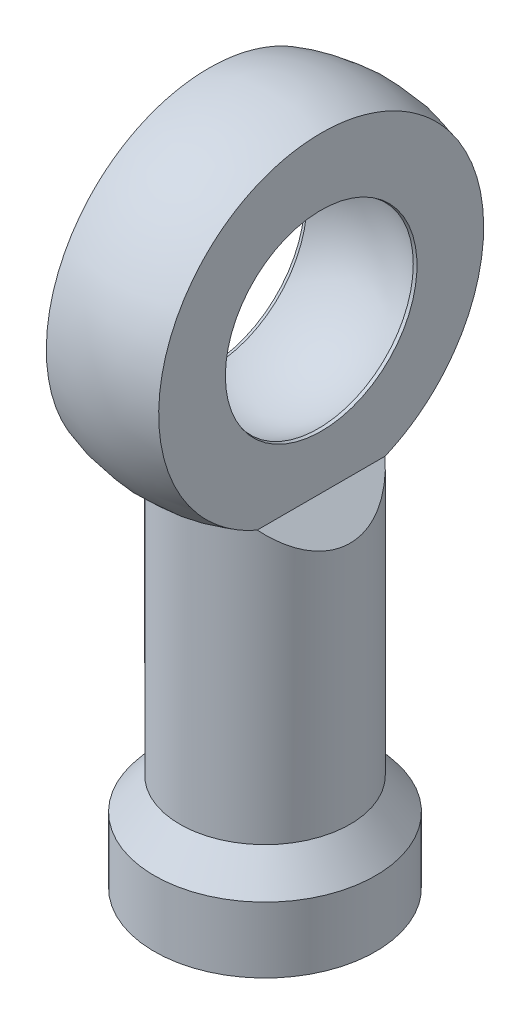
SolidWorks part; units mm, degrees
material "Rotulas (CuZn40)"
ref_plane "Alzado" through (0, 0, 0) normal (0, 0, 1) x (1, 0, 0)
ref_plane "Planta" through (0, 0, 0) normal (0, 1, 0) x (1, 0, 0)
ref_plane "Vista lateral" through (0, 0, 0) normal (1, 0, 0) x (0, 0, -1)
sketch "Croquis1" plane through (0, 0, 0) normal (0, 0, 1) x (1, 0, 0)
  line L1 (-5, -8.7755) -> (-5, -24.7755)
  line L2 (-5, -24.7755) -> (-6.5, -26.6381)
  line L3 (-6.5, -26.6381) -> (-6.5, -30.5)
  line L4 (-6.5, -30.5) -> (0, -30.5)
  line L5 (0, 10.1) -> (0, 6.4)
  line L6 (0, -6.4) -> (0, -30.5)
  arc A0 (0, 6.4) -> (0, -6.4) centre (0, 0) ccw
  arc A1 (0, 10.1) -> (-5, -8.7755) centre (0, 0) ccw
  dimension "D3" = 12.8
  dimension "D4" = 20.2
  dimension "D2" = 30.5
  dimension "D6" = 16
revolve "Revolución1" add sketch "Croquis1" angle 360 about L6
sketch "Croquis2" plane through (0, 0, 0) normal (0, 0, 1) x (1, 0, 0)
  line L0 (6.3, -11.7755) -> (3.3, -8.7755)
  line L2 (3.3, -8.7755) -> (3.3, 15.0059)
  line L3 (3.3, 15.0059) -> (11.3269, 15.0059)
  line L4 (11.3269, 15.0059) -> (10.7202, -11.7755)
  line L5 (10.7202, -11.7755) -> (6.3, -11.7755)
  line L6 (-3.3, -8.7755) -> (-3.3, 15.0059)
  line L7 (-3.3, 15.0059) -> (-11.844, 15.0059)
  line L8 (-11.844, 15.0059) -> (-11.844, -11.7755)
  line L9 (-11.844, -11.7755) -> (-6.3, -11.7755)
  line L10 (-6.3, -11.7755) -> (-3.3, -8.7755)
  dimension "D2" = 3
  dimension "D3" = 3
  dimension "D5" = 3
  dimension "D6" = 3
extrude "Cortar-Extruir1" cut sketch "Croquis2" against normal through all both and the other way through all
sketch "Croquis5" plane through (0, -30.5, 0) normal (0, -1, 0) x (1, 0, 0)
  circle A0 centre (0, 0) radius 3
extrude "Cortar-Extruir3" cut sketch "Croquis5" against normal blind 22
fillet "Redondeo5" radius 0.3 1 edges at (3, -30.5, 0)
chamfer "Chaflán1" distance 0.2 angle 45 2 edges at (-3.3, 0, -5.4836) (3.3, 0, 5.4836)
